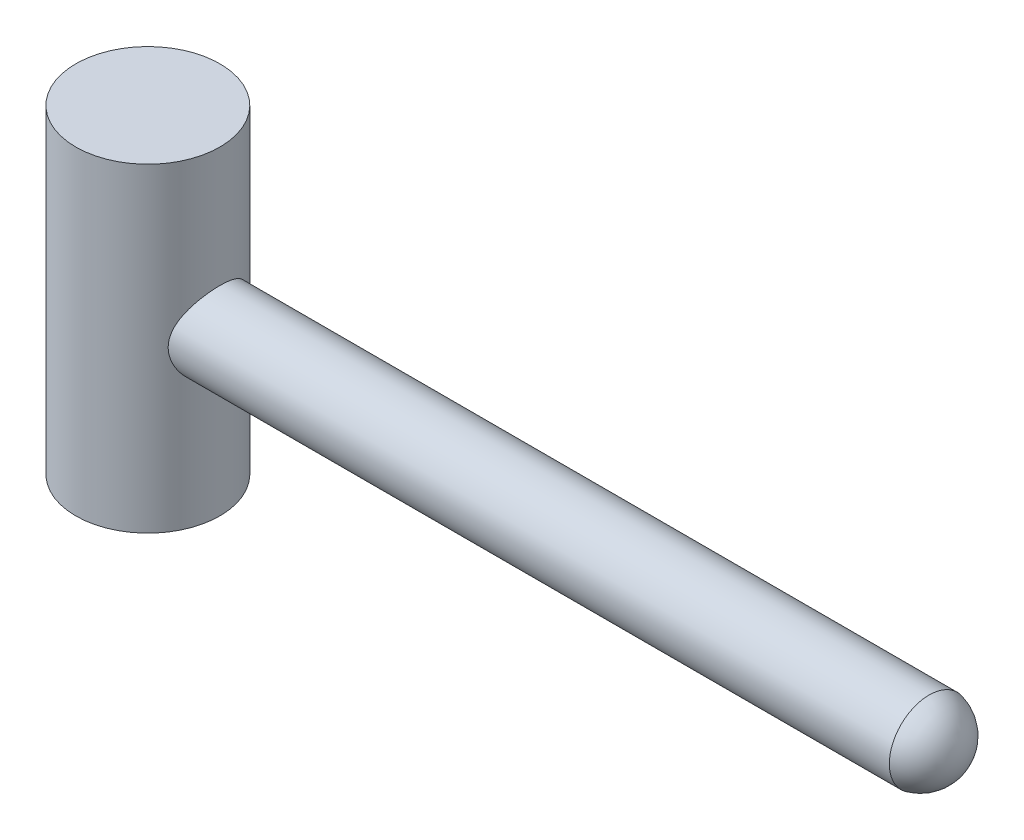
SolidWorks part; units mm, degrees
ref_plane "Front Plane" through (0, 0, 0) normal (0, 0, 1) x (1, 0, 0)
ref_plane "Top Plane" through (0, 0, 0) normal (0, 1, 0) x (1, 0, 0)
ref_plane "Right Plane" through (0, 0, 0) normal (1, 0, 0) x (0, 0, -1)
sketch "Sketch2" plane through (0, 0, 0) normal (0, 1, 0) x (1, 0, 0)
  circle A0 centre (0, 0) radius 11.4427
  dimension "D1" = 22.8854
extrude "Boss-Extrude1" add sketch "Sketch2" along normal blind 50.7111
sketch "Sketch3" plane through (0, 0, 0) normal (1, 0, 0) x (0, 0, -1)
  circle A0 centre (0, 25.3555) radius 6.3182
  point P2 (0, 0)
  dimension "D1" = 12.6365
  dimension "D2" = 25.3555
extrude "Boss-Extrude2" add sketch "Sketch3" against normal up to surface (114.4598 mm away) from offset 124 separate body contours A0 up to face at (0, 50.7111, 11.4427)
dome "Dome1" faces to dome 1 distance 5.08 reverse direction no elliptical dome no face at (124, 25.3555, -6.3182) parameters "D1"=5.08
